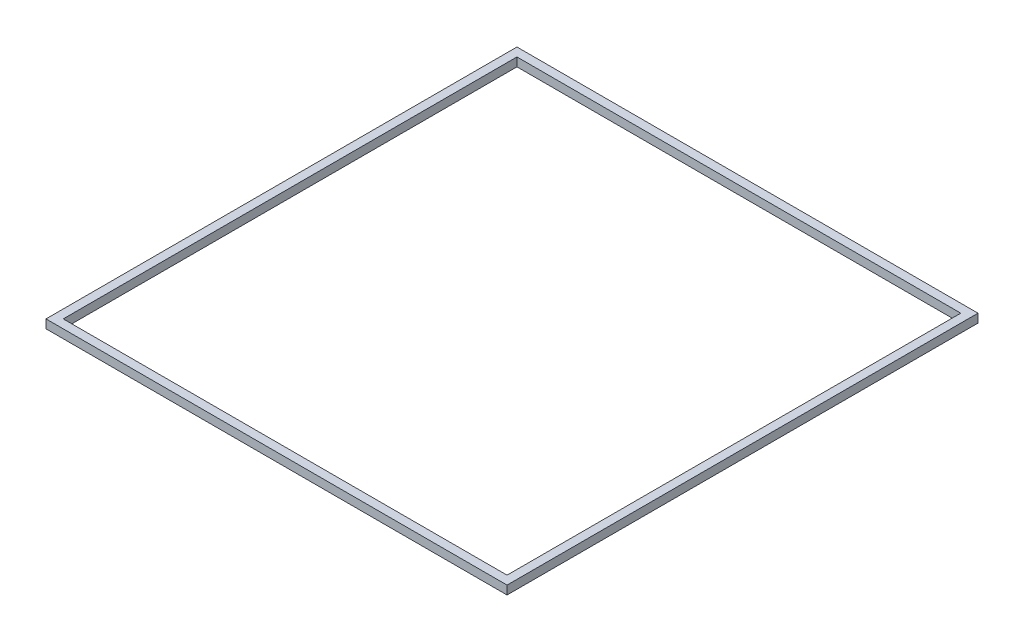
SolidWorks part; units mm, degrees
material "Silicon Rubber"
ref_plane "Front Plane" through (0, 0, 0) normal (0, 0, 1) x (1, 0, 0)
ref_plane "Top Plane" through (0, 0, 0) normal (0, 1, 0) x (1, 0, 0)
ref_plane "Right Plane" through (0, 0, 0) normal (1, 0, 0) x (0, 0, -1)
sketch "Sketch1" plane through (0, 0, 0) normal (0, 1, 0) x (1, 0, 0)
  line L1 (0, 0) -> (85, 0)
  line L2 (0, 0) -> (0, 86.825)
  line L3 (0, 86.825) -> (85, 86.825)
  line L4 (85, 0) -> (85, 86.825)
  line L5 (1.5875, 1.5875) -> (83.4125, 1.5875)
  line L6 (1.5875, 1.5875) -> (1.5875, 85.2375)
  line L7 (1.5875, 85.2375) -> (83.4125, 85.2375)
  line L8 (83.4125, 1.5875) -> (83.4125, 85.2375)
  dimension "D1" = 85
  dimension "D2" = 86.825
  dimension "D3" = 1.5875
  dimension "D4" = 1.5875
  dimension "D5" = 1.5875
  dimension "D6" = 1.5875
extrude "Boss-Extrude1" add sketch "Sketch1" along normal blind 1.5875
